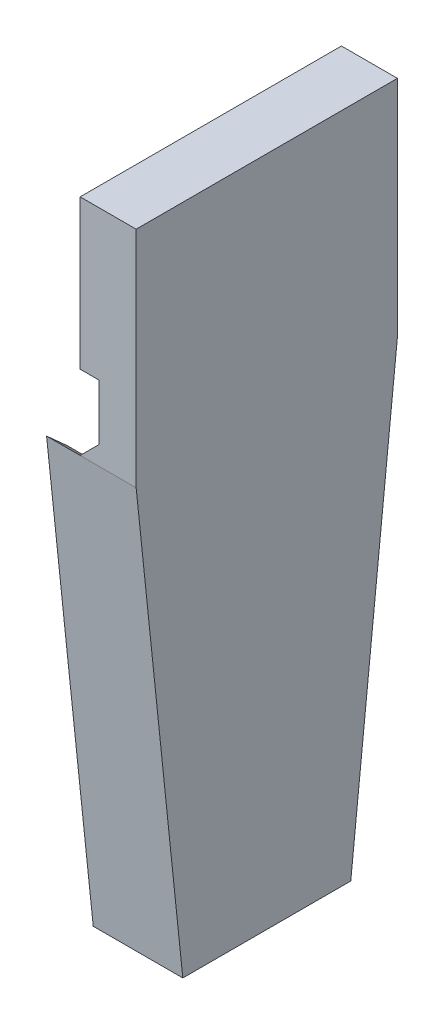
SolidWorks part; units mm, degrees
material "ABS PC"
ref_plane "前视基准面" through (0, 0, 0) normal (0, 0, 1) x (1, 0, 0)
ref_plane "上视基准面" through (0, 0, 0) normal (0, 1, 0) x (1, 0, 0)
ref_plane "右视基准面" through (0, 0, 0) normal (1, 0, 0) x (0, 0, -1)
sketch "草图1" plane through (0, 0, 0) normal (0, 0, 1) x (1, 0, 0)
  line L0 (60.6458, 0.7205) -> (40, 0.7205) construction
  line L1 (54.2884, 0.7205) -> (62.2884, 0.7205)
  line L2 (54.2884, 0.7205) -> (54.2884, -13.2795)
  line L3 (56.2884, -12.451) -> (60.2884, -16.451)
  line L4 (62.2884, 0.7205) -> (62.2884, -13.2795)
  line L5 (54.2884, -13.2795) -> (62.2884, -21.2795)
  line L6 (62.2884, -21.2795) -> (62.2884, -13.2795)
  line L7 (60.2884, -16.451) -> (60.2884, -13.2795)
  line L8 (60.2884, -1.2795) -> (60.2884, -13.2795)
  line L9 (44.3556, 10) -> (44.3556, 0) construction
  line L10 (56.2884, -5.2795) -> (56.2884, -12.451)
  line L11 (60.2884, -1.2795) -> (56.2884, -5.2795)
  line L13 (56.2884, -1.2795) -> (56.2884, -12.451) construction
  line L14 (56.2884, -1.2795) -> (60.2884, -1.2795) construction
  circle A0 centre (54.2884, 0.7205) radius 2
  dimension "D5" = 4
  dimension "D1" = 8
  dimension "D2" = 9.9329
  dimension "D3" = 8
  dimension "D4" = 2
extrude "凸台-拉伸1" add sketch "草图1" along normal blind 2.5 and the other way blind 2.5 contours L1 A0 L2 | L2 L5 L6 L4 L1 | L10 L3 L7 L8 L11 region at (54.0055, 1.0035, 0)
sketch "草图2" plane through (62.2884, 0, 0) normal (1, 0, 0) x (0, 0, -1)
  line L0 (-7, -3.2795) -> (-4.5, -27.2795)
  line L1 (-7, 8.7205) -> (7, 8.7205)
  line L2 (-7, 8.7205) -> (-7, -3.2795)
  line L4 (7, 8.7205) -> (7, -3.2795)
  line L5 (-7, 8.7205) -> (7, -3.2795) construction
  line L6 (-7, -3.2795) -> (7, 8.7205) construction
  line L7 (-4.5, -27.2795) -> (4.5, -27.2795)
  line L8 (4.5, -27.2795) -> (7, -3.2795)
  line L9 (2.5, 0.7205) -> (-2.5, 0.7205) construction
  point P0 (0, 2.7205)
  point P10 (0, 0.7205)
  point P11 (0, -27.2795)
  dimension "D1" = 9
  dimension "D2" = 14
  dimension "D3" = 12
  dimension "D4" = 24
  dimension "D5" = 8
  dimension "D6" = 24
extrude "凸台-拉伸2" add sketch "草图2" along normal blind 3 contours L0 L7 L8 L4 L1 L2
sketch "草图4" plane through (62.2884, 0, 0) normal (-1, 0, 0) x (0, 0, 1)
  line L0 (-7, -0.2795) -> (7, -0.2795)
  line L6 (7, -3.2795) -> (7, 8.7205)
  line L7 (7, 8.7205) -> (-7, 8.7205)
  line L8 (-7, 8.7205) -> (-7, -3.2795)
  line L9 (-7, -3.2795) -> (-4.5, -27.2795)
  line L10 (-4.5, -27.2795) -> (4.5, -27.2795)
  line L11 (4.5, -27.2795) -> (7, -3.2795)
  line L12 (7, -3.2795) -> (7, 8.7205)
  line L13 (7, 8.7205) -> (-7, 8.7205)
  line L14 (-7, 8.7205) -> (-7, -3.2795)
  line L15 (-7, -3.2795) -> (-4.5, -27.2795)
  line L16 (-4.5, -27.2795) -> (4.5, -27.2795)
  line L17 (4.5, -27.2795) -> (7, -3.2795)
  line M7 (2.5, 0.7205) -> (2.5, -21.2795)
  line M8 (2.5, -21.2795) -> (-2.5, -21.2795)
  line M9 (-2.5, -21.2795) -> (-2.5, 0.7205)
  line M11 (7, -3.2795) -> (7, 8.7205)
  line M13 (-7, 8.7205) -> (-7, -3.2795)
  line M14 (-7, -3.2795) -> (-4.5, -27.2795)
  line M15 (-4.5, -27.2795) -> (4.5, -27.2795)
  line M16 (4.5, -27.2795) -> (7, -3.2795)
  dimension "D2" = 3
  dimension "D1" = 0
extrude "凸台-拉伸3" add sketch "草图4" along normal blind 1.8 contours L0 M13 M14 M15 M16 M11 M7 M8 M9 | L0 M9 M8 M7 region at (62.2884, -0.5836, -4.75) region at (62.2884, -10.7795, 0)
sketch "草图5" plane through (0, 0, 0) normal (0, 0, 1) x (1, 0, 0)
  line L0 (62.2884, -27.2795) -> (62.2884, -3.2795)
  line L1 (65.2884, -27.2795) -> (60.4884, -27.2795) construction
  line L2 (62.2884, 6.7205) -> (47.884, 6.7205)
  line L3 (62.2884, -3.2795) -> (63.2884, -2.2795)
  line L4 (63.2884, -2.2795) -> (63.2884, 6.7205)
  line L5 (63.2884, 6.7205) -> (62.2884, 6.7205)
  line L6 (62.2884, 8.7205) -> (62.2884, -0.2795) construction
  line L7 (62.2884, 6.7205) -> (62.2884, 8.7205)
  line L8 (62.2884, 8.7205) -> (65.2884, 8.7205)
  line L9 (65.2884, 8.7205) -> (65.2884, -27.2795)
  line L10 (65.2884, -27.2795) -> (62.2884, -27.2795)
  line L11 (47.884, 6.7205) -> (47.884, -27.2795)
  line L12 (47.884, -27.2795) -> (62.2884, -27.2795)
  dimension "D1" = 3
  dimension "D2" = 2
  dimension "D3" = 1
  dimension "D4" = 135
  dimension "D5" = 24
extrude "切除-拉伸1" cut sketch "草图5" against normal through all both and the other way through all contours L11 L12 L0 L3 L4 L5 L2 region at (55.2326, -10.0465, 0)
sketch "草图6" plane through (62.2884, 0, 0) normal (-1, 0, 0) x (0, 0, 1)
  line L0 (7, -3.2795) -> (5.8904, -4.2795)
  line L4 (-4.5, -27.2795) -> (4.5, -27.2795)
  line L5 (-7, -3.2795) -> (-4.5, -27.2795)
  line L6 (7, -3.2795) -> (-7, -3.2795)
  line L7 (4.5, -27.2795) -> (7, -3.2795)
  line L8 (-4.5, -27.2795) -> (4.5, -27.2795)
  line L9 (-7, -3.2795) -> (-4.5, -27.2795)
  line L10 (7, -3.2795) -> (-7, -3.2795)
  line L11 (4.5, -27.2795) -> (7, -3.2795)
  line L12 (-5.8904, -4.2795) -> (-7, -3.2795)
  line L16 (-3.5988, -26.2795) -> (3.5988, -26.2795)
  line L17 (-5.8904, -4.2795) -> (-3.5988, -26.2795)
  line L18 (5.8904, -4.2795) -> (-5.8904, -4.2795)
  line L19 (3.5988, -26.2795) -> (5.8904, -4.2795)
  line L20 (-3.5988, -26.2795) -> (3.5988, -26.2795)
  line L21 (-5.8904, -4.2795) -> (-3.5988, -26.2795)
  line L22 (5.8904, -4.2795) -> (-5.8904, -4.2795)
  line L23 (3.5988, -26.2795) -> (5.8904, -4.2795)
  line M25 (-7, -3.2795) -> (-4.5, -27.2795)
  line M26 (-4.5, -27.2795) -> (4.5, -27.2795)
  line M27 (4.5, -27.2795) -> (7, -3.2795)
  dimension "D1" = 0
  dimension "D2" = 1
sketch "草图7" plane through (63.2884, 0, 0) normal (-1, 0, 0) x (0, 0, 1)
  line L0 (7, 0.7205) -> (5.5, 6.7205)
  line L1 (7, 6.7205) -> (7, -2.2795) construction
  line L2 (-7, 6.7205) -> (7, 6.7205) construction
  line L3 (5.5, 6.7205) -> (7, 6.7205)
  line L4 (7, 6.7205) -> (7, 0.7205)
  line L5 (-5.5, 6.7205) -> (-7, 6.7205)
  line L6 (-7, 6.7205) -> (-7, -2.2795) construction
  line L7 (-7, 6.7205) -> (-7, 0.7205)
  line L8 (-7, 0.7205) -> (-5.5, 6.7205)
  line L9 (-6, 6.7205) -> (-6, 4.7205)
  line L10 (6, 6.7205) -> (6, 4.7205)
  line M11 (7, 6.7205) -> (-7, 6.7205)
  line M12 (-7, 6.7205) -> (-7, -2.2795)
  line M14 (7, -2.2795) -> (7, 6.7205)
  dimension "D1" = 1.5
  dimension "D2" = 6
  dimension "D3" = 1.5
  dimension "D4" = 6
  dimension "D5" = 1
  dimension "D6" = 1
shell "抽壳1" thickness 1 removed face at (63.2884, 2.2205, 0) removed face at (62.7884, -2.7795, 0) removed face at (62.2884, -15.2795, 0)
extrude "凸台-拉伸4" add sketch "草图7" along normal blind 1 contours L9 L5 L8 M12 | L10 L0 M11 M14 region at (63.2884, 4.5539, 6.5833) region at (63.2884, 4.5539, -6.5833)
extrude "凸台-拉伸5" add sketch "草图6" along normal blind 1.8 contours L23 L20 L21 L12 L0 M25 M26 M27 region at (62.2884, -15.2507, 5.4736)
